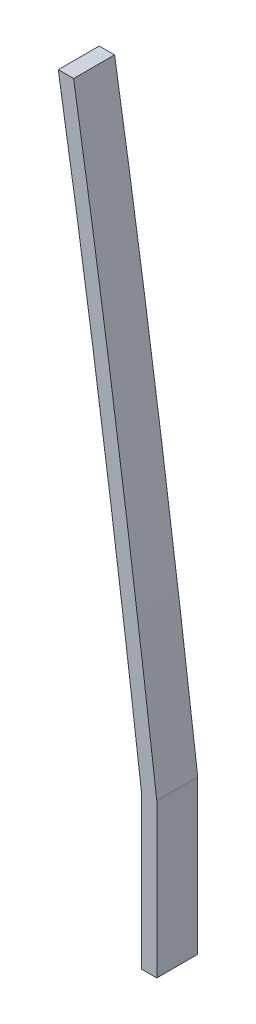
SolidWorks part; units mm, degrees
material "6061-T6 (SS)"
ref_plane "Front Plane" through (0, 0, 0) normal (0, 0, 1) x (1, 0, 0)
ref_plane "Top Plane" through (0, 0, 0) normal (0, 1, 0) x (1, 0, 0)
ref_plane "Right Plane" through (0, 0, 0) normal (1, 0, 0) x (0, 0, -1)
sketch "DrivingNCurve" plane through (0, 0, 0) normal (0, 0, 1) x (1, 0, 0)
  line L0 (0, 385.228) -> (0, 3.506) construction
  spline S0 degree 4 poles (0, 385.228) (0.0045, 385.2267) (0.0132, 385.2236) (0.0294, 385.2144) (0.0592, 385.1923) (0.097, 385.1581) (0.1416, 385.1109) (0.1989, 385.0434) (0.2618, 384.9616) (0.3301, 384.865) (0.4035, 384.7536) (0.5034, 384.5931) (0.6458, 384.3475) (0.866, 383.9344) (1.2174, 383.2068) (1.7643, 381.9446) (2.6328, 379.6932) (4.0081, 375.6581) (6.1157, 368.6433) (9.4701, 355.9866) (13.7425, 337.6251) (18.6001, 314.4216) (23.7202, 287.7134) (27.9886, 263.8616) (31.4807, 243.3881) (34.8574, 222.8956) (38.1273, 202.3855) (41.2779, 181.8569) (44.3218, 161.3121) (46.792, 144.182) (48.7299, 130.472) (50.6307, 116.7578) (52.4958, 103.0369) (54.3256, 89.3144) (55.8974, 77.2983) (57.2228, 67.004) (58.315, 58.411) (59.1779, 51.5583) (60.038, 44.6584) (60.8804, 37.8396) (61.7309, 30.8805) (62.5461, 24.1545) (63.3998, 17.0278) (64.1616, 10.6214) (65.1753, 1.9872) (65.9149, -4.3801) (67.1789, -15.3706) (68.0768, -23.362) (69.0329, -31.8885) (69.4716, -35.9125) (69.7782, -38.6853) knots 0 0 0 0 0 0.000043 0.000086 0.000172 0.000344 0.000517 0.000689 0.000996 0.001303 0.001616 0.001929 0.002754 0.003942 0.005968 0.00944 0.015541 0.026373 0.045596 0.07753 0.137266 0.201636 0.266005 0.330374 0.362559 0.394744 0.459113 0.523482 0.555667 0.587852 0.620036 0.652221 0.684406 0.716591 0.748775 0.764868 0.78096 0.797052 0.813145 0.829237 0.845329 0.861422 0.877514 0.893606 0.909699 0.932274 0.954849 0.977425 1 1 1 1 1 construction
  spline S1 degree 4 poles (0, 385.228) (0.0045, 385.2267) (0.0132, 385.2236) (0.0294, 385.2144) (0.0592, 385.1923) (0.097, 385.1581) (0.1416, 385.1109) (0.1989, 385.0434) (0.2618, 384.9616) (0.3301, 384.865) (0.4035, 384.7536) (0.5034, 384.5931) (0.6458, 384.3475) (0.866, 383.9344) (1.2174, 383.2068) (1.7643, 381.9446) (2.6328, 379.6932) (4.0081, 375.6581) (6.1157, 368.6433) (9.4701, 355.9866) (13.7425, 337.6251) (18.6001, 314.4216) (23.7202, 287.7134) (27.9886, 263.8616) (31.4807, 243.3881) (34.8574, 222.8956) (38.1273, 202.3855) (41.2779, 181.8569) (44.3218, 161.3121) (46.792, 144.182) (48.7299, 130.472) (50.6307, 116.7578) (52.4958, 103.0369) (54.3256, 89.3144) (55.8974, 77.2983) (57.2228, 67.004) (58.315, 58.411) (59.1779, 51.5583) (60.038, 44.6584) (60.8804, 37.8396) (61.7309, 30.8805) (62.5461, 24.1545) (63.3998, 17.0278) (64.1616, 10.6214) (64.8523, 4.7383) (65.223, 1.5639) (65.405, 0) knots 0 0 0 0 0 0.000043 0.000086 0.000172 0.000344 0.000517 0.000689 0.000996 0.001303 0.001616 0.001929 0.002754 0.003942 0.005968 0.00944 0.015541 0.026373 0.045596 0.07753 0.137266 0.201636 0.266005 0.330374 0.362559 0.394744 0.459113 0.523482 0.555667 0.587852 0.620036 0.652221 0.684406 0.716591 0.748775 0.764868 0.78096 0.797052 0.813145 0.829237 0.845329 0.861422 0.877514 0.893606 0.909699 0.909699 0.909699 0.909699 0.909699
  dimension "D1" = 65.405
sketch "Sketch3" plane through (0, 0, 0) normal (0, 0, 1) x (1, 0, 0)
  line L1 (1.807, 0) -> (56.4679, 0) construction
  line L6 (25.9303, 228.6) -> (30.6928, 228.6)
  line L7 (56.4679, 47.625) -> (56.4679, 0)
  line L8 (51.7054, 47.625) -> (51.7054, 0)
  line L9 (51.7054, 0) -> (56.4679, 0)
  spline S1 degree 3 poles (25.9303, 228.6) (28.8351, 210.9886) (34.3585, 175.7206) (40.7106, 131.5422) (45.505, 96.1604) (48.3893, 74.0255) (50.3489, 58.5339) (51.2613, 51.2132) (51.6211, 48.3072) (51.7054, 47.625) knots 0.158553 0.158553 0.158553 0.158553 0.216148 0.273742 0.302539 0.331336 0.345734 0.352934 0.355143 0.355143 0.355143 0.355143
  spline S4 degree 3 poles (1682.4363, -1994.8995) (-11.3816, 395.8533) (-2.3648, 383.1789) (-2.2904, 383.0706) (-2.2871, 383.0657) (-2.2794, 383.0541) (-2.2751, 383.0475) (-2.2623, 383.0275) (-2.2538, 383.0141) (-2.2289, 382.9736) (-2.2127, 382.9463) (-2.1649, 382.8641) (-2.1341, 382.8088) (-2.0436, 382.6416) (-1.9858, 382.5288) (-1.8169, 382.1881) (-1.7104, 381.9581) (-1.4009, 381.2635) (-1.2079, 380.7945) (-0.6494, 379.38) (-0.306, 378.4258) (0.6865, 375.5506) (1.2908, 373.6148) (3.0317, 367.7859) (4.0867, 363.8688) (6.1052, 356.0129) (7.0637, 352.072) (8.9175, 344.1756) (9.8112, 340.2195) (12.4227, 328.3365) (14.0713, 320.3943) (17.2501, 304.4866) (18.7788, 296.5207) (23.2329, 272.5985) (26.0267, 256.618) (31.3816, 224.6185) (33.9401, 208.599) (41.3396, 160.4982) (45.9079, 128.3754) (52.3449, 80.1364) (54.4199, 64.0463) (56.553, 46.9427) (56.6781, 45.9377) (56.9281, 43.9254) (57.0521, 42.925) (57.301, 40.9125) (57.4248, 39.9092) (57.6107, 38.3997) (57.673, 37.8937) (57.7966, 36.8874) (57.8592, 36.3775) (58.0443, 34.868) (58.1695, 33.8439) (58.3538, 32.3343) (58.4156, 31.8277) (58.5383, 30.8213) (58.5992, 30.321) (58.7215, 29.3145) (58.7816, 28.8199) (58.9037, 27.8134) (58.9634, 27.3212) (59.0853, 26.3146) (59.145, 25.8209) (59.2666, 24.8144) (59.3269, 24.3144) (59.4482, 23.3078) (59.5094, 22.7992) (59.6304, 21.7925) (59.6919, 21.2806) (59.8127, 20.274) (59.8736, 19.7657) (59.9941, 18.759) (60.0537, 18.2611) (60.1439, 17.506) (60.173, 17.2628) (60.2331, 16.7594) (60.2617, 16.5194) (60.3218, 16.0161) (60.3501, 15.7784) (60.4101, 15.275) (60.4382, 15.0387) (60.4981, 14.5354) (60.5263, 14.2989) (60.5861, 13.7955) (60.6145, 13.5565) (60.6743, 13.0531) (60.7032, 12.8092) (60.7629, 12.3058) (60.7927, 12.0547) (60.8523, 11.5513) (60.8831, 11.291) (60.9278, 10.9135) (60.9436, 10.7798) (60.9733, 10.5281) (60.9894, 10.3922) (61.0191, 10.1405) (61.0354, 10.0025) (61.0651, 9.7508) (61.0817, 9.6108) (61.1114, 9.3591) (61.1281, 9.2171) (61.1578, 8.9654) (61.1748, 8.8215) (61.2044, 8.5698) (61.2216, 8.4243) (61.2438, 8.2355) (61.2524, 8.1622) (61.2673, 8.0364) (61.2759, 7.9629) (61.2907, 7.837) (61.2994, 7.7633) (61.3142, 7.6374) (61.3229, 7.5637) (61.3377, 7.4378) (61.3464, 7.3639) (61.3612, 7.2381) (61.3699, 7.1642) (61.3847, 7.0384) (61.3934, 6.9646) (61.4082, 6.8387) (61.4168, 6.7651) (61.4316, 6.6392) (61.4403, 6.5657) (61.455, 6.4399) (61.4636, 6.3667) (61.4858, 6.1779) (61.5029, 6.0325) (61.5325, 5.7808) (61.5493, 5.6372) (61.5789, 5.3854) (61.5954, 5.2443) (61.625, 4.9925) (61.6412, 4.8543) (61.6707, 4.6026) (61.6865, 4.4675) (61.716, 4.2157) (61.7315, 4.0839) (61.7757, 3.7063) (61.8053, 3.4534) (61.8495, 3.0757) (61.8636, 2.955) (61.8931, 2.7032) (61.9067, 2.5865) (61.9362, 2.3348) (61.9493, 2.2222) (61.9787, 1.9704) (61.9914, 1.8617) (62.0135, 1.6729) (62.0197, 1.6199) (62.0344, 1.494) (62.0405, 1.4418) (62.0552, 1.3159) (62.0612, 1.2645) (62.0759, 1.1386) (62.0818, 1.0879) (62.0964, 0.962) (62.1023, 0.912) (62.117, 0.7862) (62.1227, 0.7368) (62.1374, 0.6109) (62.1431, 0.5621) (62.1577, 0.4362) (62.1634, 0.388) (62.178, 0.2621) (62.1836, 0.2144) (62.1983, 0.0885) (62.2038, 0.0412) (62.2184, -0.0847) (62.2239, -0.1316) (62.5801, -3.1918) (58.983, 27.6935) (408.6938, -2977.1088) knots -0.00037 -0.00037 -0.00037 -0.00037 0.000006 0.000006 0.000024 0.000024 0.000048 0.000048 0.000095 0.000095 0.00019 0.00019 0.00038 0.00038 0.00076 0.00076 0.001521 0.001521 0.003042 0.003042 0.006083 0.006083 0.012167 0.012167 0.024333 0.024333 0.0365 0.0365 0.048667 0.048667 0.073 0.073 0.097333 0.097333 0.146 0.146 0.194666 0.194666 0.292 0.292 0.340666 0.340666 0.343708 0.343708 0.34675 0.34675 0.349791 0.349791 0.351312 0.351312 0.352833 0.352833 0.355875 0.355875 0.357395 0.357395 0.358916 0.358916 0.360437 0.360437 0.361958 0.361958 0.363479 0.363479 0.365 0.365 0.36652 0.36652 0.368041 0.368041 0.369562 0.369562 0.371083 0.371083 0.371843 0.371843 0.372604 0.372604 0.373364 0.373364 0.374125 0.374125 0.374885 0.374885 0.375645 0.375645 0.376406 0.376406 0.377166 0.377166 0.377927 0.377927 0.378307 0.378307 0.378687 0.378687 0.379067 0.379067 0.379447 0.379447 0.379828 0.379828 0.380208 0.380208 0.380588 0.380588 0.380778 0.380778 0.380968 0.380968 0.381158 0.381158 0.381348 0.381348 0.381539 0.381539 0.381729 0.381729 0.381919 0.381919 0.382109 0.382109 0.382299 0.382299 0.382489 0.382489 0.382869 0.382869 0.383249 0.383249 0.38363 0.38363 0.38401 0.38401 0.38439 0.38439 0.38477 0.38477 0.385531 0.385531 0.385911 0.385911 0.386291 0.386291 0.386671 0.386671 0.387052 0.387052 0.387242 0.387242 0.387432 0.387432 0.387622 0.387622 0.387812 0.387812 0.388002 0.388002 0.388192 0.388192 0.388382 0.388382 0.388572 0.388572 0.388763 0.388763 0.388953 0.388953 0.389143 0.389143 0.398195 0.398195 0.398195 0.398195 only from (-2.2971, 383.0803) to (62.2513, -0.367)
  spline S5 degree 3 poles (30.6928, 228.6) (32.6567, 216.598) (34.5575, 204.5857) (41.3396, 160.4982) (45.9079, 128.3754) (52.3449, 80.1364) (54.4199, 64.0463) (56.441, 47.8409) (56.4545, 47.7329) (56.4679, 47.625) knots 0.158182 0.158182 0.158182 0.158182 0.194666 0.194666 0.292 0.292 0.340666 0.340666 0.340993 0.340993 0.340993 0.340993
  dimension "D2" = 228.6
  dimension "D3" = 4.7625
  dimension "D5" = 47.625
  dimension "D6" = 4.7625
  dimension "D1" = 3.175
extrude "Boss-Extrude1" add sketch "Sketch3" along normal blind 6.35 and the other way blind 6.35 contours S5 L7 L9 L8 S1 L6
